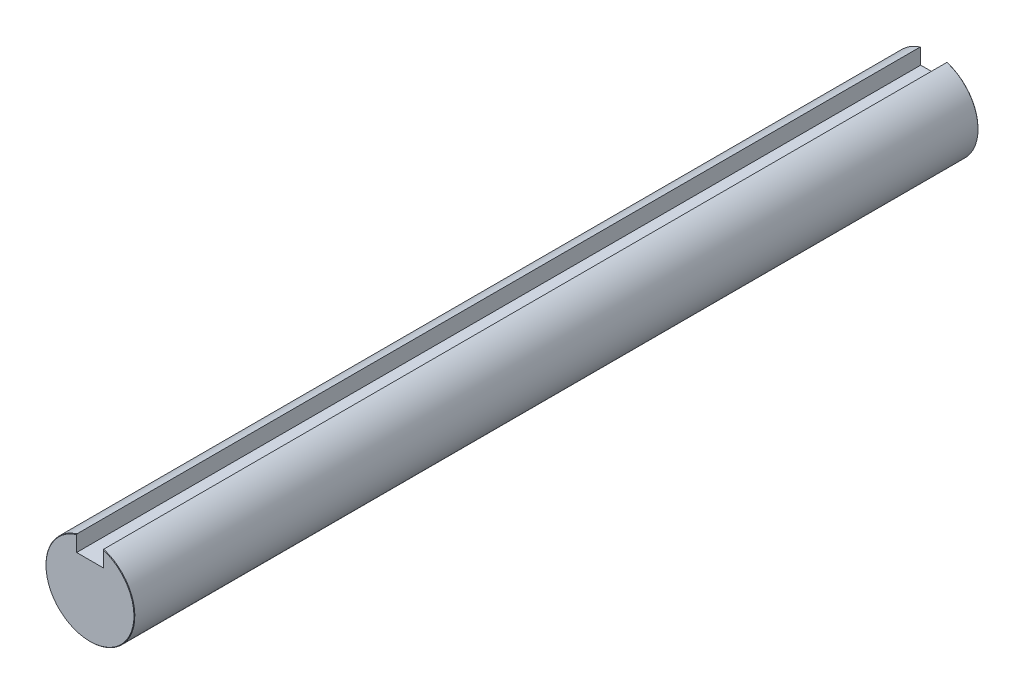
SolidWorks part; units mm, degrees
ref_plane "Front Plane" through (0, 0, 0) normal (0, 0, 1) x (1, 0, 0)
ref_plane "Top Plane" through (0, 0, 0) normal (0, 1, 0) x (1, 0, 0)
ref_plane "Right Plane" through (0, 0, 0) normal (1, 0, 0) x (0, 0, -1)
sketch "Sketch1" plane through (0, 0, 0) normal (1, 0, 0) x (0, 0, -1)
  line L0 (0, 0) -> (0, 5) construction
  line L1 (-47.5, 5) -> (47.5, 5)
  line L2 (-47.5, 5) -> (-47.5, -5)
  line L3 (-47.5, -5) -> (47.5, -5)
  line L4 (47.5, 5) -> (47.5, -5)
  line L5 (-47.5, 5) -> (47.5, -5) construction
  line L6 (-47.5, -5) -> (47.5, 5) construction
  line L7 (0, 0) -> (0, -5) construction
  point P0 (0, 0)
  point P8 (-36, 5)
  point P10 (36, 5)
  point P11 (-32.1667, -5)
  point P12 (34.221, -5)
  dimension "Diameter" = 10
  dimension "Length" = 95
  dimension "D1" = 11.5
  dimension "D2" = 11.5
  dimension "Keyway Length" = 95
  dimension "D3" = 13.279
  dimension "D5" = 15.3333
sketch "Sketch2" plane through (0, 0, 0) normal (0, 0, 1) x (1, 0, 0)
  line L0 (0, 0) -> (0, 5) construction
  line L2 (1.5, 2.9697) -> (-1.5, 2.9697)
  line L3 (1.5, 2.9697) -> (1.5, 4.7697)
  line L4 (1.5, 4.7697) -> (-1.5, 4.7697)
  line L5 (-1.5, 2.9697) -> (-1.5, 4.7697)
  line L6 (1.5, 2.9697) -> (-1.5, 4.7697) construction
  line L7 (1.5, 4.7697) -> (-1.5, 2.9697) construction
  circle A0 centre (0, 0) radius 5
  point P3 (0, 3.8697)
  dimension "Keyway Width" = 3
  dimension "Keyway Depth" = 1.8
sketch "Sketch3" plane through (0, 0, 0) normal (0, 0, 1) x (1, 0, 0)
  line L1 (-1.5, 2.9697) -> (-1.5, 4.7697) construction
  line L2 (1.5, 2.9697) -> (-1.5, 2.9697) construction
  line L3 (1.5, 2.9697) -> (1.5, 4.7697) construction
  line L5 (-1.5, 2.9697) -> (-1.5, 4.7697)
  line L6 (1.5, 2.9697) -> (-1.5, 2.9697)
  line L7 (1.5, 2.9697) -> (1.5, 4.7697)
  circle A0 centre (0, 0) radius 5 construction
  arc A1 (-1.5, 4.7697) -> (1.5, 4.7697) centre (0, 0) ccw
extrude "Boss-Extrude1" add sketch "Sketch3" along normal up to vertex (47.5 mm away) and the other way up to vertex (47.5 mm away) up to point (0, 5, 47.5) other way up to point (0, 5, -47.5)
chamfer "Chamfer1" distance 0.05 angle 45 2 edges at (0, -5, 47.5) (0, -5, -47.5)
equation "\"D2@Sketch1\"=1.15*\"Diameter@Sketch1\""
equation "\"D1@Sketch1\"=\"D2@Sketch1\""
equation "\"D1@Chamfer1\"=\"Diameter@Sketch1\"*.005"
equation "\"D3@Sketch1\"=\"D2@Sketch1\"/(2*tan(.5236*180/pi))*4/3"
equation "\"D5@Sketch1\" = 4 / 3 * \"D2@Sketch1\""
